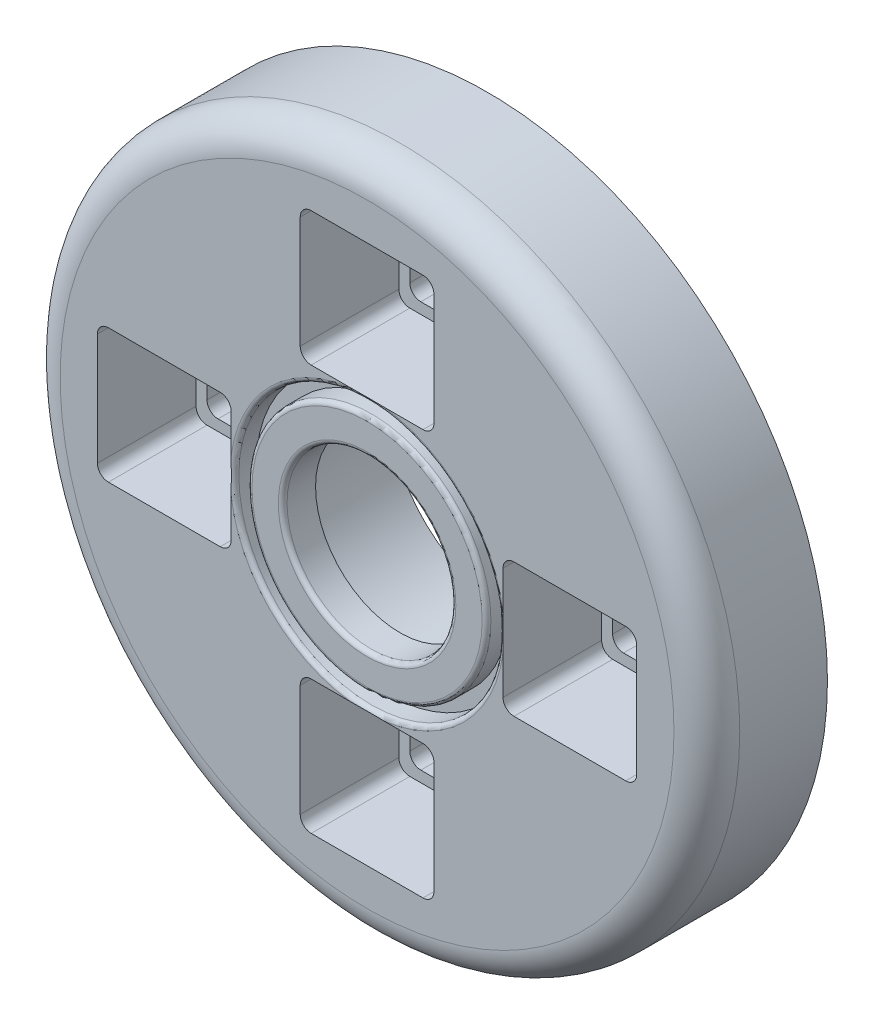
SolidWorks part; units mm, degrees
ref_plane "Front" through (0, 0, 0) normal (0, 0, 1) x (1, 0, 0)
ref_plane "Top" through (0, 0, 0) normal (0, 1, 0) x (1, 0, 0)
ref_plane "Right" through (0, 0, 0) normal (1, 0, 0) x (0, 0, -1)
sketch "Çizim1" plane through (0, 0, 0) normal (0, 0, 1) x (1, 0, 0)
  circle A0 centre (0, 0) radius 135
  dimension "D1" = 270
extrude "Yükseklik-Ekstrüzyon1" add sketch "Çizim1" along normal blind 60
sketch "Çizim2" plane through (0, 0, 0) normal (0, 0, 1) x (1, 0, 0)
  circle A1 centre (0, 0) radius 155
  dimension "D1" = 310
extrude "Yükseklik-Ekstrüzyon2" add sketch "Çizim2" along normal blind 50 from offset 10
sketch "Çizim3" plane through (0, 0, 0) normal (0, 0, -1) x (-1, 0, 0)
  circle A0 centre (0, 0) radius 55
  dimension "D1" = 110
extrude "Kes-Ekstrüzyon1" cut sketch "Çizim3" against normal blind 741
sketch "Çizim4" plane through (0, 0, 0) normal (0, 0, -1) x (-1, 0, 0)
  circle A0 centre (0, 0) radius 55
  circle A1 centre (0, 0) radius 38.5
  dimension "D1" = 77
  dimension "D2" = 110
extrude "Yükseklik-Ekstrüzyon3" add sketch "Çizim4" against normal up to surface (60 mm away) from offset 50 up to face at (55, 0, 60) offset against normal yes
sketch "Çizim5" plane through (0, 0, 60) normal (0, 0, 1) x (1, 0, 0)
  circle A0 centre (0, 0) radius 38.5 construction
  circle A1 centre (0, 0) radius 155
  circle A2 centre (0, 0) radius 155
  circle A3 centre (0, 0) radius 38.5
  dimension "D1" = 0
extrude "Yükseklik-Ekstrüzyon4" add sketch "Çizim5" along normal blind 5
sketch "Çizim6" plane through (0, 0, 65) normal (0, 0, 1) x (1, 0, 0)
  circle A0 centre (0, 0) radius 54.5
  circle A1 centre (0, 0) radius 60.5
  dimension "D1" = 109
  dimension "D2" = 121
extrude "Kes-Ekstrüzyon2" cut sketch "Çizim6" against normal blind 10
fillet "Radyus2" radius 2 3 edges at (60.5, 0, 65) (54.5, 0, 65) (38.5, 0, 65)
fillet "Fillet1" radius 15 1 edges at (155, 0, 65)
sketch "Sketch1" plane through (0, 0, 0) normal (0, 0, -1) x (-1, 0, 0)
  line L0 (0, 0) -> (-92.5, 0)
  line L1 (25.5, 123) -> (-25.5, 123)
  line L2 (-118, 30.5) -> (-67, 30.5)
  line L3 (-123, 25.5) -> (-123, -25.5)
  line L4 (-118, -30.5) -> (-67, -30.5)
  line L5 (-62, 25.5) -> (-62, -25.5)
  line L6 (-123, 30.5) -> (-62, -30.5) construction
  line L7 (-123, -30.5) -> (-62, 30.5) construction
  line L8 (30.5, 118) -> (30.5, 67)
  line L9 (25.5, 62) -> (-25.5, 62)
  line L10 (-30.5, 118) -> (-30.5, 67)
  line L11 (123, -25.5) -> (123, 25.5)
  line L12 (118, -30.5) -> (67, -30.5)
  line L13 (62, -25.5) -> (62, 25.5)
  line L14 (118, 30.5) -> (67, 30.5)
  line L15 (-25.5, -123) -> (25.5, -123)
  line L16 (-30.5, -118) -> (-30.5, -67)
  line L17 (-25.5, -62) -> (25.5, -62)
  line L18 (30.5, -118) -> (30.5, -67)
  arc A0 (-123, -25.5) -> (-118, -30.5) centre (-118, -25.5) ccw
  arc A1 (-67, -30.5) -> (-62, -25.5) centre (-67, -25.5) ccw
  arc A2 (-67, 30.5) -> (-62, 25.5) centre (-67, 25.5) cw
  arc A3 (-118, 30.5) -> (-123, 25.5) centre (-118, 25.5) ccw
  arc A4 (30.5, 118) -> (25.5, 123) centre (25.5, 118) ccw
  arc A5 (-25.5, 123) -> (-30.5, 118) centre (-25.5, 118) ccw
  arc A6 (30.5, 67) -> (25.5, 62) centre (25.5, 67) cw
  arc A7 (-30.5, 67) -> (-25.5, 62) centre (-25.5, 67) ccw
  arc A8 (118, -30.5) -> (123, -25.5) centre (118, -25.5) ccw
  arc A9 (123, 25.5) -> (118, 30.5) centre (118, 25.5) ccw
  arc A10 (67, -30.5) -> (62, -25.5) centre (67, -25.5) cw
  arc A11 (67, 30.5) -> (62, 25.5) centre (67, 25.5) ccw
  arc A12 (-30.5, -118) -> (-25.5, -123) centre (-25.5, -118) ccw
  arc A13 (25.5, -123) -> (30.5, -118) centre (25.5, -118) ccw
  arc A14 (-30.5, -67) -> (-25.5, -62) centre (-25.5, -67) cw
  arc A15 (30.5, -67) -> (25.5, -62) centre (25.5, -67) ccw
  point P58 (0, 0)
  dimension "D4" = 5
  dimension "D1" = 92.5
  dimension "D2" = 61
  dimension "D3" = 61
  dimension "D5" = 4
extrude "Cut-Extrude1" cut sketch "Sketch1" against normal through all from offset 20 contours L2 A3 L3 A0 L4 A1 L5 A2 | L10 A7 L9 A6 L8 A4 L1 A5 | L14 A11 L13 A10 L12 A8 L11 A9 | L18 A15 L17 A14 L16 A12 L15 A13 region at (0, 92.5, 0) region at (92.5, 29.6373, 0) region at (-92.5, 0, 0) region at (0, -92.5, 0) offset against normal yes
sketch "Sketch2" plane through (0, 0, 0) normal (0, 0, -1) x (-1, 0, 0)
  line L0 (0, 0) -> (-92.5, 0)
  line L1 (20.5, 118) -> (-20.5, 118)
  line L2 (-113, 25.5) -> (-72, 25.5)
  line L3 (-118, 20.5) -> (-118, -20.5)
  line L4 (-113, -25.5) -> (-72, -25.5)
  line L5 (-67, 20.5) -> (-67, -20.5)
  line L6 (-118, 25.5) -> (-67, -25.5) construction
  line L7 (-118, -25.5) -> (-67, 25.5) construction
  line L8 (25.5, 113) -> (25.5, 72)
  line L9 (20.5, 67) -> (-20.5, 67)
  line L10 (-25.5, 113) -> (-25.5, 72)
  line L11 (118, -20.5) -> (118, 20.5)
  line L12 (113, -25.5) -> (72, -25.5)
  line L13 (67, -20.5) -> (67, 20.5)
  line L14 (113, 25.5) -> (72, 25.5)
  line L15 (-20.5, -118) -> (20.5, -118)
  line L16 (-25.5, -113) -> (-25.5, -72)
  line L17 (-20.5, -67) -> (20.5, -67)
  line L18 (25.5, -113) -> (25.5, -72)
  arc A0 (-113, 25.5) -> (-118, 20.5) centre (-113, 20.5) ccw
  arc A1 (-118, -20.5) -> (-113, -25.5) centre (-113, -20.5) ccw
  arc A2 (-72, -25.5) -> (-67, -20.5) centre (-72, -20.5) ccw
  arc A3 (-72, 25.5) -> (-67, 20.5) centre (-72, 20.5) cw
  arc A4 (-20.5, 118) -> (-25.5, 113) centre (-20.5, 113) ccw
  arc A5 (25.5, 113) -> (20.5, 118) centre (20.5, 113) ccw
  arc A6 (25.5, 72) -> (20.5, 67) centre (20.5, 72) cw
  arc A7 (-25.5, 72) -> (-20.5, 67) centre (-20.5, 72) ccw
  arc A8 (118, 20.5) -> (113, 25.5) centre (113, 20.5) ccw
  arc A9 (113, -25.5) -> (118, -20.5) centre (113, -20.5) ccw
  arc A10 (72, -25.5) -> (67, -20.5) centre (72, -20.5) cw
  arc A11 (72, 25.5) -> (67, 20.5) centre (72, 20.5) ccw
  arc A12 (20.5, -118) -> (25.5, -113) centre (20.5, -113) ccw
  arc A13 (-25.5, -113) -> (-20.5, -118) centre (-20.5, -113) ccw
  arc A14 (-25.5, -72) -> (-20.5, -67) centre (-20.5, -72) cw
  arc A15 (25.5, -72) -> (20.5, -67) centre (20.5, -72) ccw
  point P58 (0, 0)
  dimension "D4" = 5
  dimension "D1" = 92.5
  dimension "D2" = 51
  dimension "D3" = 51
  dimension "D5" = 4
extrude "Cut-Extrude2" cut sketch "Sketch2" against normal through all contours A3 L2 A0 L3 A1 L4 A2 L5 | L10 A7 L9 A6 L8 A5 L1 A4 | L14 A11 L13 A10 L12 A9 L11 A8 | L18 A15 L17 A14 L16 A13 L15 A12 region at (0, 92.5, 0) region at (92.5, 24.7788, 0) region at (-92.5, 0, 0) region at (0, -92.5, 0)
